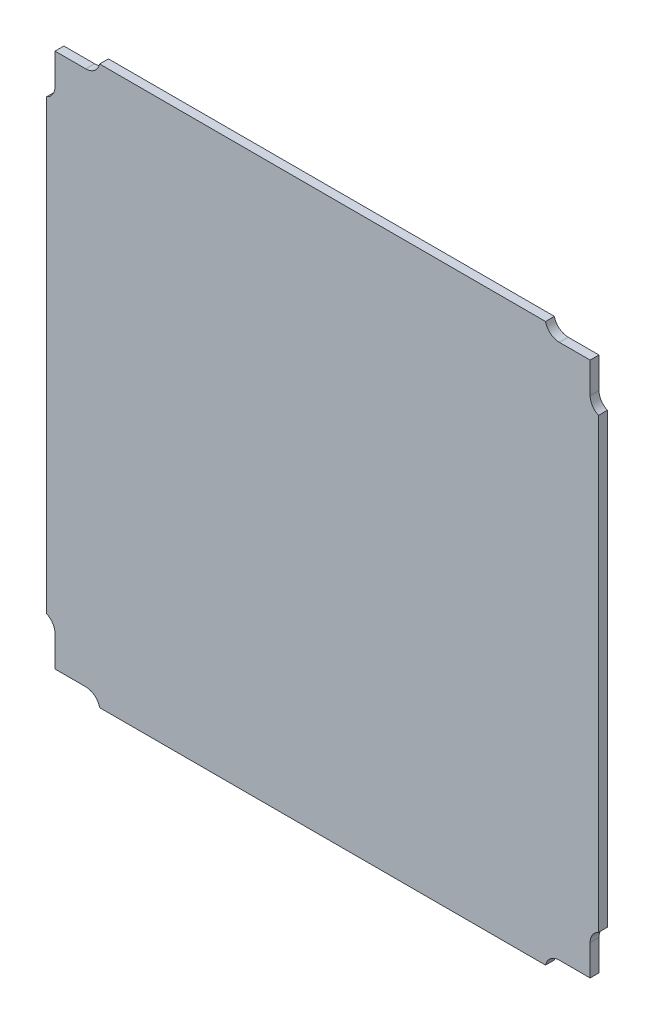
SolidWorks part; units mm, degrees
ref_plane "Front Plane" through (0, 0, 0) normal (0, 0, 1) x (1, 0, 0)
ref_plane "Top Plane" through (0, 0, 0) normal (0, 1, 0) x (1, 0, 0)
ref_plane "Right Plane" through (0, 0, 0) normal (1, 0, 0) x (0, 0, -1)
sketch "Sketch1" plane through (0, 0, 0) normal (0, 0, 1) x (1, 0, 0)
  line L0 (-40, 50) -> (-40, 48)
  line L1 (-50, -50) -> (50, -50)
  line L2 (-50, -50) -> (-50, 50)
  line L3 (-50, 50) -> (50, 50)
  line L4 (50, -50) -> (50, 50)
  line L5 (-50, -50) -> (50, 50) construction
  line L6 (-50, 50) -> (50, -50) construction
  line L7 (-50, 50) -> (-40, 50)
  line L8 (-50, 50) -> (-50, 40)
  line L9 (-40, 48) -> (-48, 48)
  line L10 (-48, 48) -> (-48, 40)
  line L11 (50, 50) -> (40, 50)
  line L12 (50, 50) -> (50, 40)
  line L13 (-48, 40) -> (-50, 40)
  line L14 (50, 40) -> (48, 40)
  line L15 (-50, -50) -> (-37.8649, -50)
  line L16 (-50, -50) -> (-50, -37.8649)
  line L17 (50, 50) -> (50, 40)
  line L18 (50, 50) -> (40, 50)
  line L19 (50, -50) -> (41.5, -50)
  line L20 (50, -50) -> (50, -41.5)
  line L21 (48, 40) -> (48, 48)
  line L22 (48, 48) -> (40, 48)
  line L23 (40, 48) -> (40, 50)
  line L24 (40, -50) -> (40, -48)
  line L25 (50, -50) -> (40, -50)
  line L26 (50, -50) -> (50, -40)
  line L27 (40, -48) -> (48, -48)
  line L28 (48, -48) -> (48, -40)
  line L29 (48, -40) -> (50, -40)
  line L30 (-50, -40) -> (-48, -40)
  line L31 (-50, -50) -> (-50, -40)
  line L32 (-50, -50) -> (-40, -50)
  line L33 (-48, -40) -> (-48, -48)
  line L34 (-48, -48) -> (-40, -48)
  line L35 (-40, -48) -> (-40, -50)
  point P0 (0, 0)
  point P38 (0, 0)
  dimension "D1" = 100
  dimension "D2" = 100
  dimension "D3" = 2
  dimension "D4" = 10
  dimension "D5" = 4
extrude "Boss-Extrude1" add sketch "Sketch1" along normal blind 1.5875 contours L1 L4 L3 L2 region at (0, 0, 0)
fillet "Fillet1" radius 2.54 8 edges at (-48, -40, 0.7937) (-40, -48, 0.7937) (40, -48, 0.7937) (48, -40, 0.7937) (48, 40, 0.7937) (40, 48, 0.7937) (-40, 48, 0.7937) (-48, 40, 0.7937)
sketch "Sketch6" plane through (0, 0, 1.5875) normal (0, 0, 1) x (1, 0, 0)
  line L0 (-40, 50) -> (40, 50) construction
  line L1 (-49.5, 50) -> (49.5, 50)
  line L2 (-49.5, 50) -> (-49.5, -50)
  line L3 (-49.5, -50) -> (49.5, -50)
  line L4 (49.5, 50) -> (49.5, -50)
  line L5 (-40, -50) -> (40, -50) construction
  line L6 (50, -40) -> (50, 40) construction
  dimension "D1" = 99
  dimension "D2" = 0.5
extrude "Cut-Extrude2" cut sketch "Sketch6" against normal through all flip side to cut
ref_axis "Axis1" through (0, 0, 0) along (0, 0, 1)
sketch "Sketch7" plane through (0, 0, 0) normal (0, 0, -1) x (-1, 0, 0)
  circle A0 centre (0, 0) radius 38.5
  dimension "D1" = 77
extrude "Boss-Extrude2" add sketch "Sketch7" along normal blind 0.1
